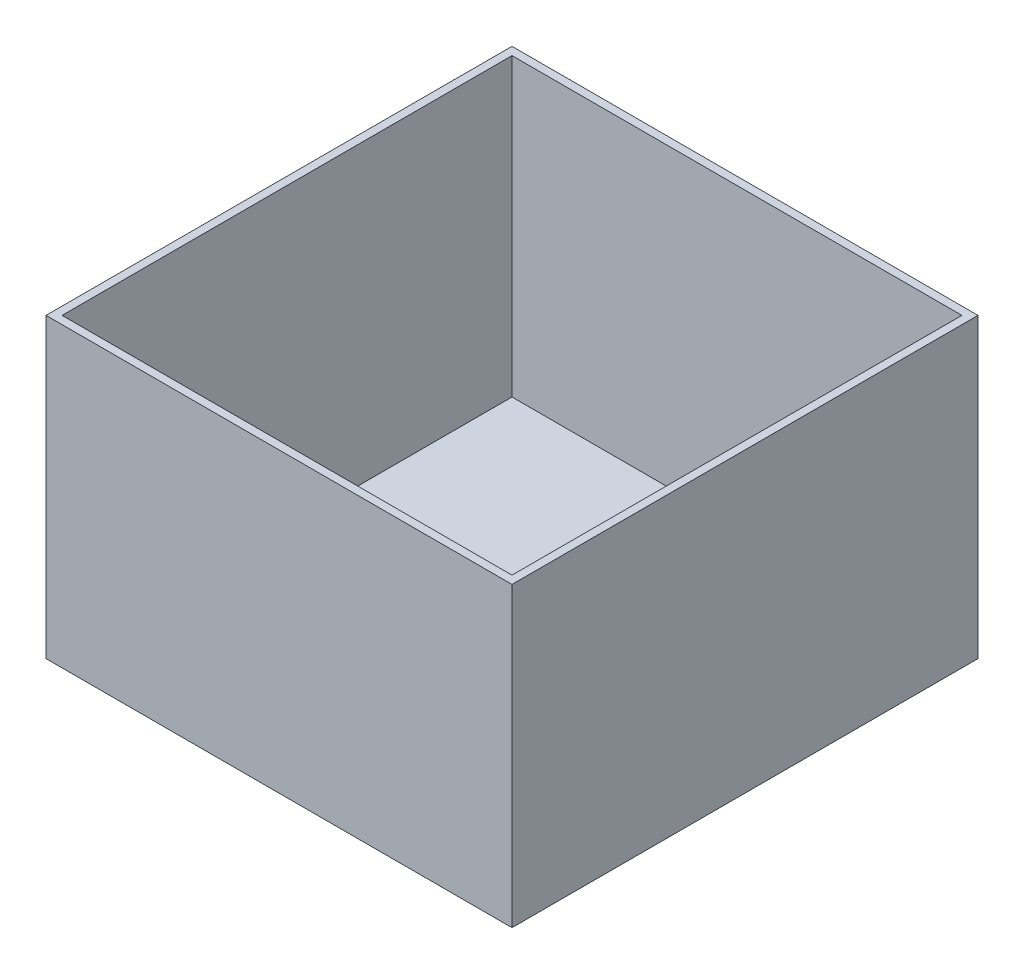
SolidWorks part; units mm, degrees
ref_plane "Front" through (0, 0, 0) normal (0, 0, 1) x (1, 0, 0)
ref_plane "Top" through (0, 0, 0) normal (0, 1, 0) x (1, 0, 0)
ref_plane "Right" through (0, 0, 0) normal (1, 0, 0) x (0, 0, -1)
sketch "Sketch1" plane through (0, 0, 0) normal (0, 1, 0) x (1, 0, 0)
  line L1 (-92.075, -92.075) -> (92.075, -92.075)
  line L2 (-92.075, -92.075) -> (-92.075, 92.075)
  line L3 (-92.075, 92.075) -> (92.075, 92.075)
  line L4 (92.075, -92.075) -> (92.075, 92.075)
  line L5 (-92.075, -92.075) -> (92.075, 92.075) construction
  line L6 (-92.075, 92.075) -> (92.075, -92.075) construction
  point P0 (0, 0)
  dimension "D1" = 184.15
  dimension "D2" = 184.15
extrude "Boss-Extrude1" add sketch "Sketch1" along normal blind 117.475
sketch "Sketch2" plane through (0, 117.475, 0) normal (0, 1, 0) x (1, 0, 0)
  line L1 (-88.9, 88.9) -> (88.9, 88.9)
  line L2 (-88.9, 88.9) -> (-88.9, -88.9)
  line L3 (-88.9, -88.9) -> (88.9, -88.9)
  line L4 (88.9, 88.9) -> (88.9, -88.9)
  line L5 (-88.9, 88.9) -> (88.9, -88.9) construction
  line L6 (-88.9, -88.9) -> (88.9, 88.9) construction
  point P0 (0, 0)
  dimension "D1" = 177.8
  dimension "D2" = 177.8
extrude "Cut-Extrude1" cut sketch "Sketch2" against normal blind 116.84
sketch "Sketch3" plane through (0, 0.635, 0) normal (0, 1, 0) x (1, 0, 0)
  line L0 (-92.075, 92.075) -> (-92.075, -92.075) construction
  line L1 (92.075, 92.075) -> (-92.075, 92.075) construction
  circle A0 centre (-1.016, 78.6514) radius 5.842
  point P4 (0, 92.075)
  dimension "D2" = 13.462
  dimension "D1" = 91.059
extrude "Boss-Extrude2" add sketch "Sketch3" along normal blind 6.604
sketch "Sketch4" plane through (0, 0.635, 0) normal (0, 1, 0) x (1, 0, 0)
  line L0 (-92.075, 0) -> (92.075, 0) construction
  line L1 (-92.075, 92.075) -> (-92.075, -92.075) construction
  line L2 (92.075, -92.075) -> (92.075, 92.075) construction
